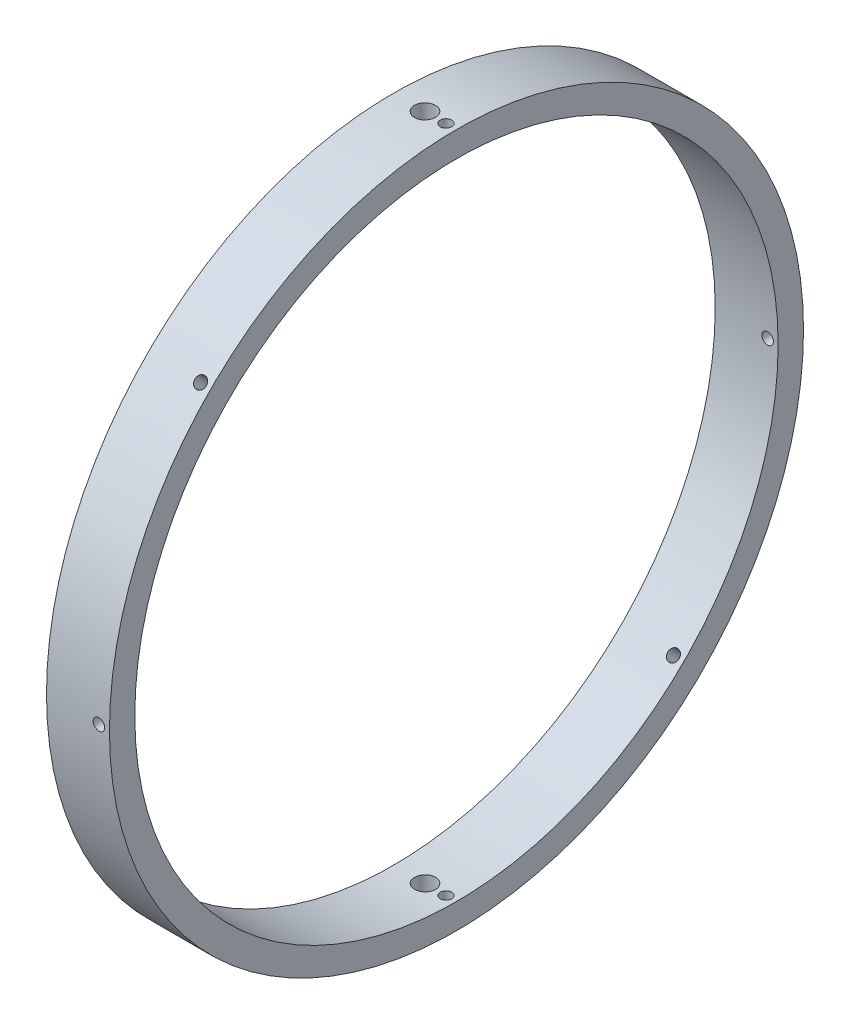
SolidWorks part; units mm, degrees
ref_plane "Front Plane" through (0, 0, 0) normal (0, 0, 1) x (1, 0, 0)
ref_plane "Top Plane" through (0, 0, 0) normal (0, 1, 0) x (1, 0, 0)
ref_plane "Right Plane" through (0, 0, 0) normal (1, 0, 0) x (0, 0, -1)
sketch "Mount Sketch" plane through (0, 0, 0) normal (0, 0, 1) x (1, 0, 0)
  line L0 (-108, 0) -> (12, 0) construction
  line L1 (-57, 92) -> (-39, 92)
  line L2 (-39, 92) -> (-39, 99.25)
  line L3 (-39, 99.25) -> (-57, 99.25)
  line L4 (-57, 99.25) -> (-57, 92)
revolve "Mount" add sketch "Mount Sketch" angle 360 about L0
ref_axis "Engine Axis" through (-38.1, 0, 0) along (-1, 0, 0)
sketch "Pin Hole Sketch" plane through (0, 0, 0) normal (0, 0, 1) x (1, 0, 0)
  line L0 (-48, 82) -> (-48, 109.25) construction
  line L1 (-48, 91) -> (-45, 91)
  line L2 (-45, 91) -> (-45, 100.25)
  line L3 (-45, 100.25) -> (-48, 100.25)
  line L4 (-48, 100.25) -> (-48, 91)
revolve "Pin Hole" cut sketch "Pin Hole Sketch" angle 360 about L0
pattern_circular "Pin Holes x2" count 2 over 360 about axis through (-38.1, 0, 0) along (-1, 0, 0) of "Pin Hole"
sketch "Screw Hole Sketch" plane through (0, 0, 0) normal (0, 0, 1) x (1, 0, 0)
  line L0 (-42, 82) -> (-42, 109.25) construction
  line L1 (-42, 91) -> (-40.35, 91)
  line L2 (-40.35, 91) -> (-40.35, 100.25)
  line L3 (-40.35, 100.25) -> (-42, 100.25)
  line L4 (-42, 100.25) -> (-42, 91)
revolve "Screw Hole" cut sketch "Screw Hole Sketch" angle 360 about L0
pattern_circular "Screw Holes x8" count 8 over 360 about axis through (-38.1, 0, 0) along (-1, 0, 0) of "Screw Hole"
